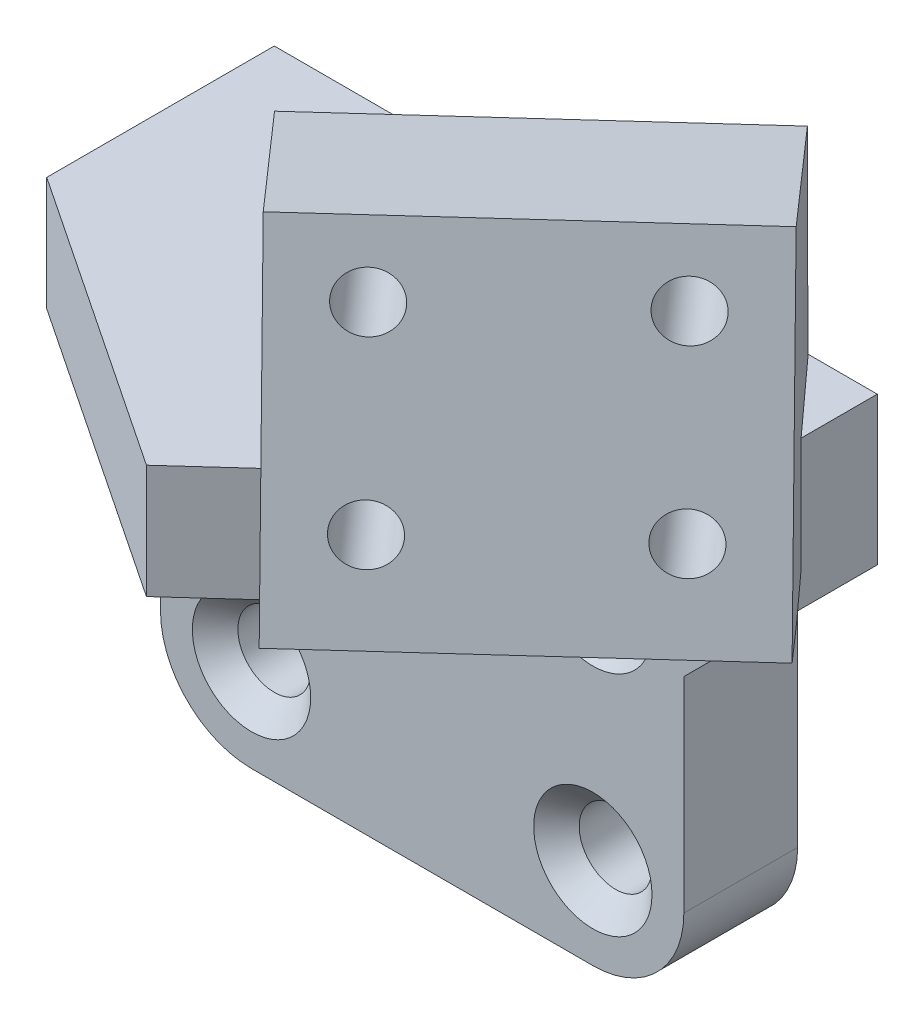
SolidWorks part; units mm, degrees
ref_plane "Front Plane" through (0, 0, 0) normal (0, 0, 1) x (1, 0, 0)
ref_plane "Top Plane" through (0, 0, 0) normal (0, 1, 0) x (1, 0, 0)
ref_plane "Right Plane" through (0, 0, 0) normal (1, 0, 0) x (0, 0, -1)
sketch "Sketch1" plane through (0, 0, 0) normal (0, 0, 1) x (1, 0, 0)
  line L1 (-7.5, 5) -> (7.5, 5) construction
  line L2 (-7.5, 5) -> (-7.5, -5) construction
  line L3 (-7.5, -5) -> (7.5, -5) construction
  line L4 (7.5, 5) -> (7.5, -5) construction
  line L5 (-7.5, 5) -> (7.5, -5) construction
  line L6 (-7.5, -5) -> (7.5, 5) construction
  line L7 (11.5, -9) -> (-11.5, -9)
  line L8 (11.5, -9) -> (11.5, 9)
  line L9 (11.5, 9) -> (-11.5, 9)
  line L10 (-11.5, -9) -> (-11.5, 9)
  line L11 (11.5, -9) -> (-11.5, 9) construction
  line L12 (11.5, 9) -> (-11.5, -9) construction
  circle A0 centre (-7.5, 5) radius 1.6
  circle A1 centre (7.5, 5) radius 1.6
  circle A2 centre (7.5, -5) radius 1.6
  circle A3 centre (-7.5, -5) radius 1.6
  point P0 (0, 0)
  point P10 (0, 0)
  dimension "D1" = 3.2
  dimension "D2" = 15
  dimension "D3" = 10
  dimension "D4" = 4
  dimension "D5" = 4
extrude "Boss-Extrude1" add sketch "Sketch1" along normal blind 5
sketch "Sketch2" plane through (0, 9, 0) normal (0, 1, 0) x (1, 0, 0)
  line L1 (-11.5, 0) -> (15, 0)
  line L2 (-11.5, 0) -> (-11.5, -20)
  line L3 (-11.5, -20) -> (15, -20) construction
  line L4 (15, 0) -> (15, -20) construction
  line L5 (0.2807, -20) -> (15, -6.644)
  line L6 (-11.5, -20) -> (0.2807, -20)
  line L8 (-12.65, 0) -> (12.65, 0) construction
  line L9 (0, -11) -> (0, 11) construction
  line L10 (15, 0) -> (15, -6.644)
  dimension "D1" = 20
  dimension "D2" = 42.22
  dimension "D3" = 15
  dimension "D4" = 15
extrude "Boss-Extrude2" add sketch "Sketch2" along normal blind 5
sketch "Sketch3" plane through (0, 14, 0) normal (0, 1, 0) x (1, 0, 0)
  line L0 (0, 0) -> (11.1086, 10.0797)
  line L1 (-12.65, 0) -> (12.65, 0) construction
  line L2 (0, -20.2547) -> (11.1086, -10.175)
  dimension "D1" = 42.22
  dimension "D2" = 15
  dimension "D3" = 15
ref_plane "Plane1" through (11.3846, 2.9873, 12.5466) normal (0.6618, 0.1736, 0.7293) x (0.7406, 0, -0.672)
chamfer "Chamfer1" distance 5 angle 45 1 edges at (11.5, 9, 2.5)
chamfer "Chamfer2" distance 1 angle 45 1 edges at (1.75, 9, 5)
sketch "Sketch4" plane through (11.3846, 2.9873, 12.5466) normal (0.6618, 0.1736, 0.7293) x (0.7406, 0, -0.672)
  line L1 (-7.7214, 21.1826) -> (8.8586, 21.1826)
  line L2 (-7.7214, 21.1826) -> (-7.7214, 6.1826)
  line L3 (-7.7214, 6.1826) -> (8.8586, 6.1826)
  line L4 (8.8586, 21.1826) -> (8.8586, 6.1826)
  line L5 (-13.2317, 11.1826) -> (6.644, 11.1826) construction
  dimension "D1" = 10
  dimension "D2" = 15
extrude "Boss-Extrude3" add sketch "Sketch4" along normal blind 2.5 separate body
sketch "Sketch5" plane through (-5.7182, 0, 5.1886) normal (-0.7406, 0, 0.672) x (0.672, 0, 0.7406)
  line L0 (13.2635, 23.8481) -> (8.5, 23.0081)
  line L1 (19.3685, -10.7752) -> (14.5151, 16.7498) construction
  line L3 (18.3303, 9.5101) -> (15.8682, 9.076) construction
  line L4 (15.7255, 24.2822) -> (13.2635, 23.8481) construction
  line L5 (13.2635, 23.8481) -> (13.7559, 23.9349)
  line L6 (13.7559, 23.9349) -> (16.3606, 9.1628)
  line L7 (16.3606, 9.1628) -> (15.4374, 9)
  line L8 (13.2635, 23.8481) -> (15.8682, 9.076) construction
  line L9 (8.5, 23.0081) -> (8.5, 9)
  line L10 (8.5, 9) -> (15.4374, 9)
  line L11 (15, 14) -> (15, 9) construction
  line L12 (7.0836, 9) -> (15, 9) construction
  dimension "D1" = 0.5
  dimension "D2" = 6.5
extrude "Boss-Extrude4" add sketch "Sketch5" against normal up to surface (16.58 mm away) up to face at (17.1756, 16.6791, 5.7459)
sketch "Sketch6" plane through (13.039, 3.4214, 14.3699) normal (0.6618, 0.1736, 0.7293) x (0.6544, -0.6085, -0.4489)
  line L0 (-1.913, 11.447) -> (-9.7758, 5.2683) construction
  line L1 (-1.913, 11.447) -> (-6.856, 17.7373) construction
  line L2 (-9.7758, 5.2683) -> (-14.7188, 11.5586) construction
  line L3 (-6.856, 17.7373) -> (-14.7188, 11.5586) construction
  line L4 (-1.913, 11.447) -> (-14.7188, 11.5586) construction
  line L5 (-9.7758, 5.2683) -> (-6.856, 17.7373) construction
  line L6 (-6.1228, 22.1289) -> (-19.1593, 11.8846) construction
  line L7 (-12.641, 17.0068) -> (-8.3159, 11.5028) construction
  line L8 (3.1453, 10.3347) -> (-6.1228, 22.1289) construction
  circle A0 centre (-14.7188, 11.5586) radius 1.2
  circle A1 centre (-6.856, 17.7373) radius 1.2
  circle A2 centre (-1.913, 11.447) radius 1.2
  circle A3 centre (-9.7758, 5.2683) radius 1.2
  point P1 (-8.3159, 11.5028)
  dimension "D4" = 2.4
  dimension "D1" = 3
  dimension "D2" = 10
  dimension "D3" = 8
extrude "Cut-Extrude1" cut sketch "Sketch6" against normal blind 8.5
chamfer "Chamfer3" distance 10 distance2 15 1 edges at (-11.5, 11.5, 20) first distance on face at (-11.5, 5.1429, 8)
fillet "Fillet1" radius 4 2 edges at (11.5, -9, 2.5) (-11.5, -9, 2.5)
chamfer "Chamfer4" distance 1 angle 45 4 edges at (-5.9, -5, 5) (9.1, -5, 5) (9.1, 5, 5) (-5.9, 5, 5)
chamfer "Chamfer5" distance 3 angle 45 1 edges at (6.1329, 14, 5.9127)
equation "\"6.00mmmm\"=8"
